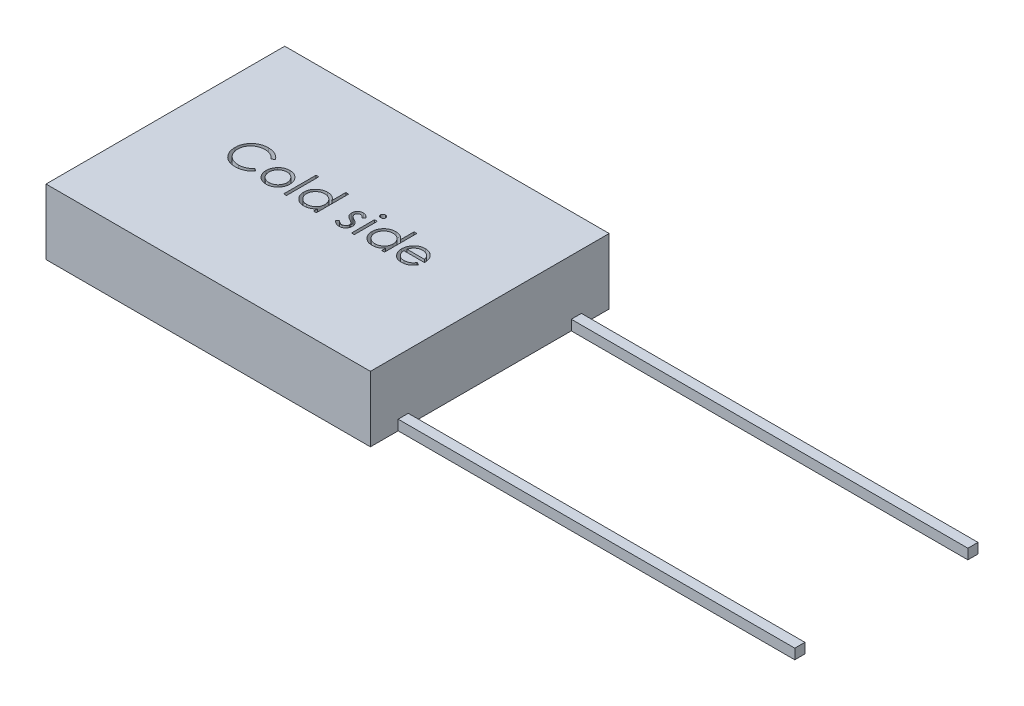
SolidWorks part; units mm, degrees
ref_plane "Front Plane" through (0, 0, 0) normal (0, 0, 1) x (1, 0, 0)
ref_plane "Top Plane" through (0, 0, 0) normal (0, 1, 0) x (1, 0, 0)
ref_plane "Right Plane" through (0, 0, 0) normal (1, 0, 0) x (0, 0, -1)
sketch "Sketch2" plane through (0, 0, 0) normal (0, 1, 0) x (1, 0, 0)
  line L0 (0, 3.01) -> (8.18, 3.01) construction
  line L1 (0, 0) -> (8.18, 0)
  line L2 (0, 0) -> (0, 6.02)
  line L3 (0, 6.02) -> (8.18, 6.02)
  line L4 (8.18, 0) -> (8.18, 6.02)
  line L5 (8.18, 5.32) -> (18.18, 5.32)
  line L6 (8.18, 5.32) -> (8.18, 5.065)
  line L7 (8.18, 5.065) -> (18.18, 5.065)
  line L8 (18.18, 5.32) -> (18.18, 5.065)
  line L9 (8.18, 3.01) -> (20.589, 3.01) construction
  line L10 (18.18, 0.7) -> (18.18, 0.955)
  line L11 (8.18, 0.955) -> (18.18, 0.955)
  line L12 (8.18, 0.7) -> (18.18, 0.7)
  dimension "D1" = 8.18
  dimension "D2" = 6.02
  dimension "D3" = 0.7
  dimension "D4" = 0.255
  dimension "D5" = 10
extrude "Boss-Extrude1" add sketch "Sketch2" along normal blind 1.65 contours L1 L4 L3 L2 region at (4.09, 0, -3.01)
extrude "Boss-Extrude2" add sketch "Sketch2<3>" along normal blind 0.255 contours L4 L12 L10 L11 | L8 L5 L4 L7 region at (13.18, 0, -0.8275) region at (13.18, 0, -5.1925)
sketch "Sketch2<3>" plane through (0, 0, 0) normal (0, 1, 0) x (1, 0, 0) same geometry as "Sketch2"
sketch "Sketch3" plane through (0, 1.65, 0) normal (0, 1, 0) x (1, 0, 0)
  text T0 "Cold side" font "Century Gothic" height in points 3
extrude "Cut-Extrude1" cut sketch "Sketch3" against normal blind 0.255
